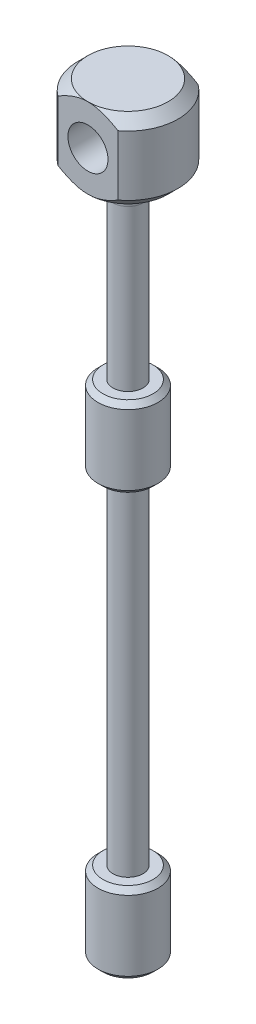
SolidWorks part; units mm, degrees
ref_plane "Front Plane" through (0, 0, 0) normal (0, 0, 1) x (1, 0, 0)
ref_plane "Top Plane" through (0, 0, 0) normal (0, 1, 0) x (1, 0, 0)
ref_plane "Right Plane" through (0, 0, 0) normal (1, 0, 0) x (0, 0, -1)
sketch "Sketch1" plane through (0, 0, 0) normal (0, 1, 0) x (1, 0, 0)
  circle A0 centre (0, 0) radius 3
  dimension "D1" = 6
extrude "Boss-Extrude1" add sketch "Sketch1" along normal blind 8
sketch "Sketch2" plane through (0, 8, 0) normal (0, 1, 0) x (1, 0, 0)
  circle A0 centre (0, 0) radius 1.5
  dimension "D1" = 3
extrude "Boss-Extrude2" add sketch "Sketch2" along normal blind 34
sketch "Sketch3" plane through (0, 42, 0) normal (0, 1, 0) x (1, 0, 0)
  circle A0 centre (0, 0) radius 3
  dimension "D1" = 6
extrude "Boss-Extrude3" add sketch "Sketch3" along normal blind 8
sketch "Sketch4" plane through (0, 50, 0) normal (0, 1, 0) x (1, 0, 0)
  circle A0 centre (0, 0) radius 1.5
  dimension "D1" = 3
extrude "Boss-Extrude4" add sketch "Sketch4" along normal blind 18
sketch "Sketch5" plane through (0, 68, 0) normal (0, 1, 0) x (1, 0, 0)
  line L0 (-3, 4) -> (3, 4)
  line L1 (-3, -4) -> (3, -4)
  arc A0 (-3, 4) -> (-3, -4) centre (0, 0) ccw
  arc A1 (3, -4) -> (3, 4) centre (0, 0) ccw
  dimension "D1" = 10
  dimension "D2" = 4
  dimension "D3" = 4
extrude "Boss-Extrude5" add sketch "Sketch5" along normal blind 8
sketch "Sketch6" plane through (0, 0, 4) normal (0, 0, 1) x (1, 0, 0)
  line L0 (-3, 76) -> (3, 76) construction
  circle A0 centre (0, 72) radius 2
  dimension "D2" = 4
  dimension "D1" = 4
extrude "Cut-Extrude1" cut sketch "Sketch6" against normal through all both and the other way through all
chamfer "Chamfer1" distance 1 angle 45 4 edges at (5, 68, 0) (-5, 68, 0) (-5, 76, 0) (5, 76, 0)
chamfer "Chamfer2" distance 0.5 angle 45 4 edges at (0, 50, 3) (0, 42, 3) (0, 8, 3) (0, 0, 3)
fillet "Fillet1" radius 2 1 edges at (0, 68, 1.5)
